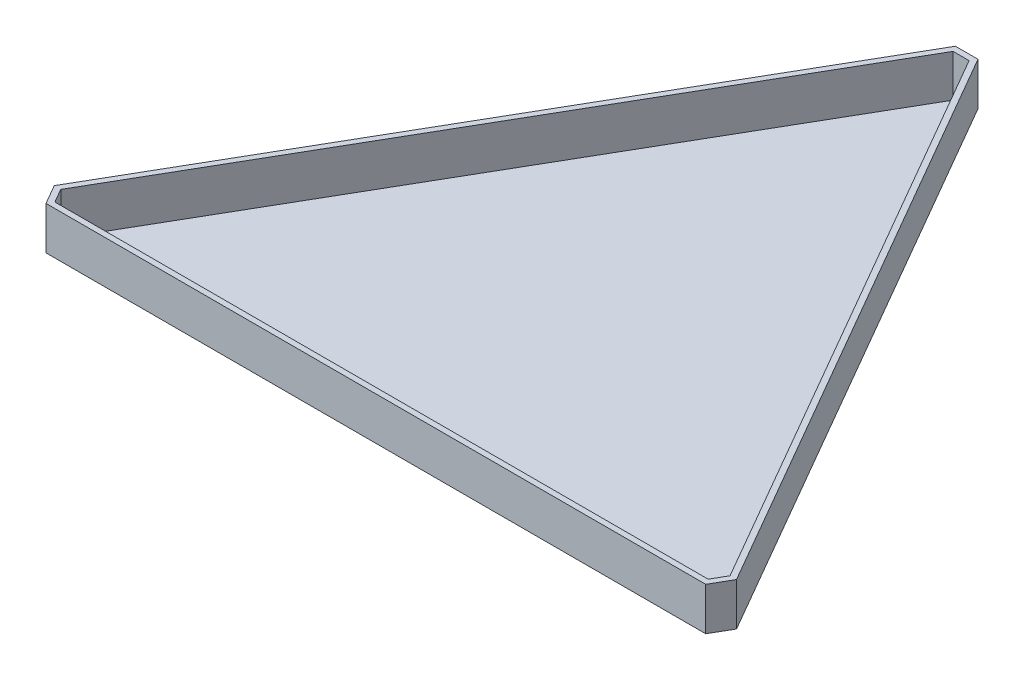
SolidWorks part; units mm, degrees
ref_plane "Front Plane" through (0, 0, 0) normal (0, 0, 1) x (1, 0, 0)
ref_plane "Top Plane" through (0, 0, 0) normal (0, 1, 0) x (1, 0, 0)
ref_plane "Right Plane" through (0, 0, 0) normal (1, 0, 0) x (0, 0, -1)
sketch "Sketch1" plane through (0, 0, 0) normal (0, 1, 0) x (1, 0, 0)
  line L0 (351.2729, 67.6655) -> (468.273, -134.9846)
  line L1 (231.428, -139.9124) -> (463.1186, -139.9124)
  line L3 (468.273, -134.9846) -> (464.2732, -141.9124)
  line L4 (230.2733, -141.9124) -> (464.2732, -141.9124)
  line L5 (230.2733, -141.9124) -> (226.2727, -134.9842)
  line L6 (226.2727, -134.9842) -> (343.2728, 67.6655)
  line L20 (343.2728, 67.6655) -> (351.2729, 67.6655)
  line L26 (231.428, -139.9124) -> (228.582, -134.9842)
  line L27 (228.582, -134.9842) -> (344.4274, 65.6656)
  line L28 (344.4274, 65.6656) -> (350.1183, 65.6656)
  line L29 (350.1183, 65.6656) -> (465.9637, -134.9846)
  line L30 (465.9637, -134.9846) -> (463.1186, -139.9124)
extrude "Boss-Extrude6" add sketch "Sketch1" along normal blind 0.2 contours L0 L3 L4 L5 L6 L20
extrude "Boss-Extrude8" add sketch "Sketch1<7>" along normal blind 15.2
sketch "Sketch1<7>" plane through (0, 0, 0) normal (0, 1, 0) x (1, 0, 0) same geometry as "Sketch1"
